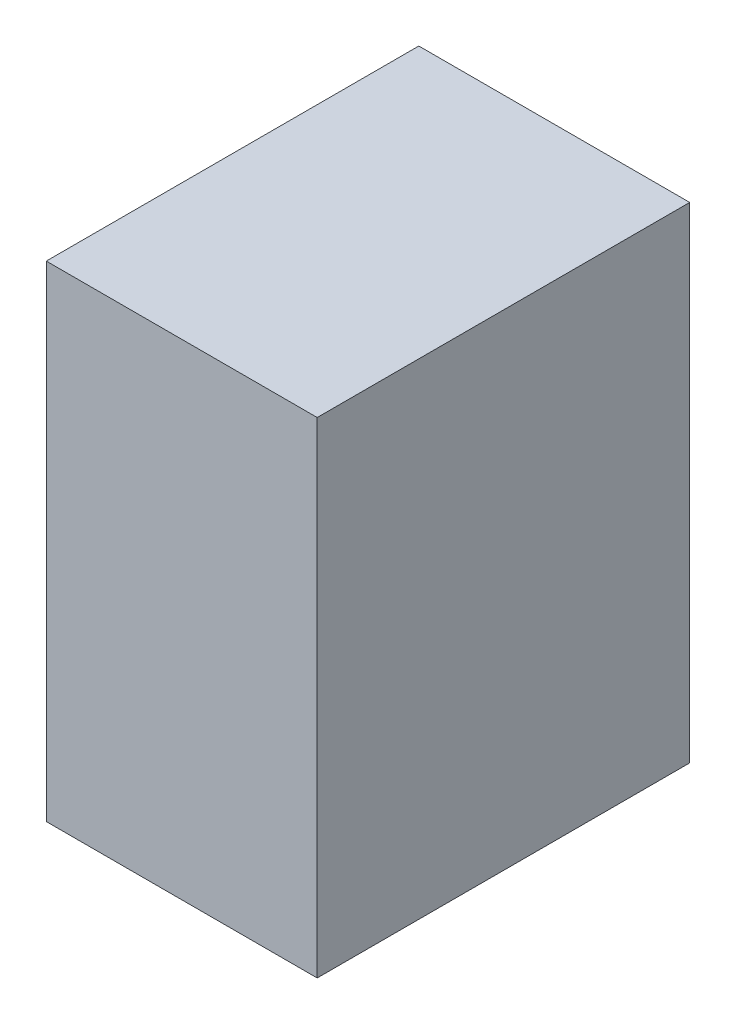
SolidWorks part; units mm, degrees
ref_plane "Front Plane" through (0, 0, 0) normal (0, 0, 1) x (1, 0, 0)
ref_plane "Top Plane" through (0, 0, 0) normal (0, 1, 0) x (1, 0, 0)
ref_plane "Right Plane" through (0, 0, 0) normal (1, 0, 0) x (0, 0, -1)
sketch "Case Sketch" plane through (0, 0, 0) normal (1, 0, 0) x (0, 0, -1)
  line L0 (-45.5, -41.5) -> (-45.5, 1.5)
  line L1 (-45.5, 1.5) -> (-78.5, 1.5)
  line L2 (-78.5, 1.5) -> (-78.5, -41.5)
  line L3 (-78.5, -41.5) -> (-45.5, -41.5)
extrude "Case" add sketch "Case Sketch" against normal blind 24
ref_axis "Engine Axis" through (1.2, 0, 0) along (-1, 0, 0)
